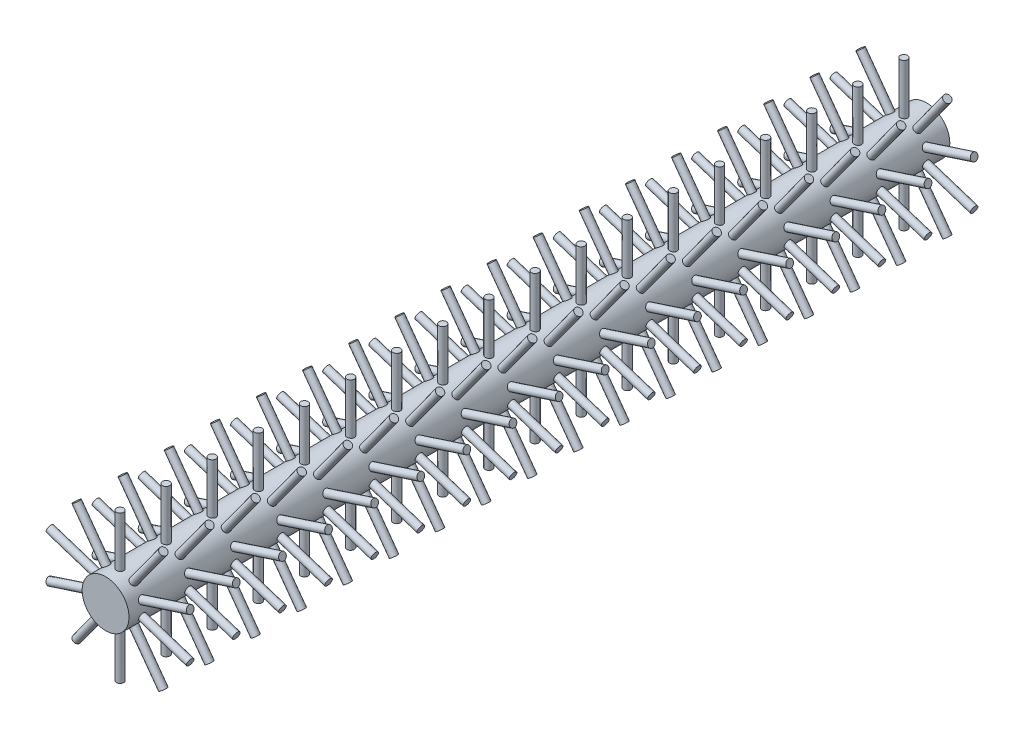
SolidWorks part; units mm, degrees
ref_plane "Front Plane" through (0, 0, 0) normal (0, 0, 1) x (1, 0, 0)
ref_plane "Top Plane" through (0, 0, 0) normal (0, 1, 0) x (1, 0, 0)
ref_plane "Right Plane" through (0, 0, 0) normal (1, 0, 0) x (0, 0, -1)
sketch "Sketch1" plane through (0, 0, 0) normal (0, 0, 1) x (1, 0, 0)
  circle A0 centre (0, 0) radius 12.7
extrude "Boss-Extrude1" add sketch "Sketch1" along normal blind 445 contours A0
sketch "Sketch2" plane through (0, 0, 0) normal (0, 1, 0) x (1, 0, 0)
  circle A0 centre (0, -12.1576) radius 2
  dimension "D1" = 4
extrude "Boss-Extrude2" add sketch "Sketch2" along normal blind 40
pattern_circular "CirPattern1" count 10 over 360 about axis through (0, 0, 445) along (0, 0, -1) of "Boss-Extrude2"
pattern_linear "LPattern1" count 18 spacing 25 along (0, 0, 1) of "CirPattern1"
